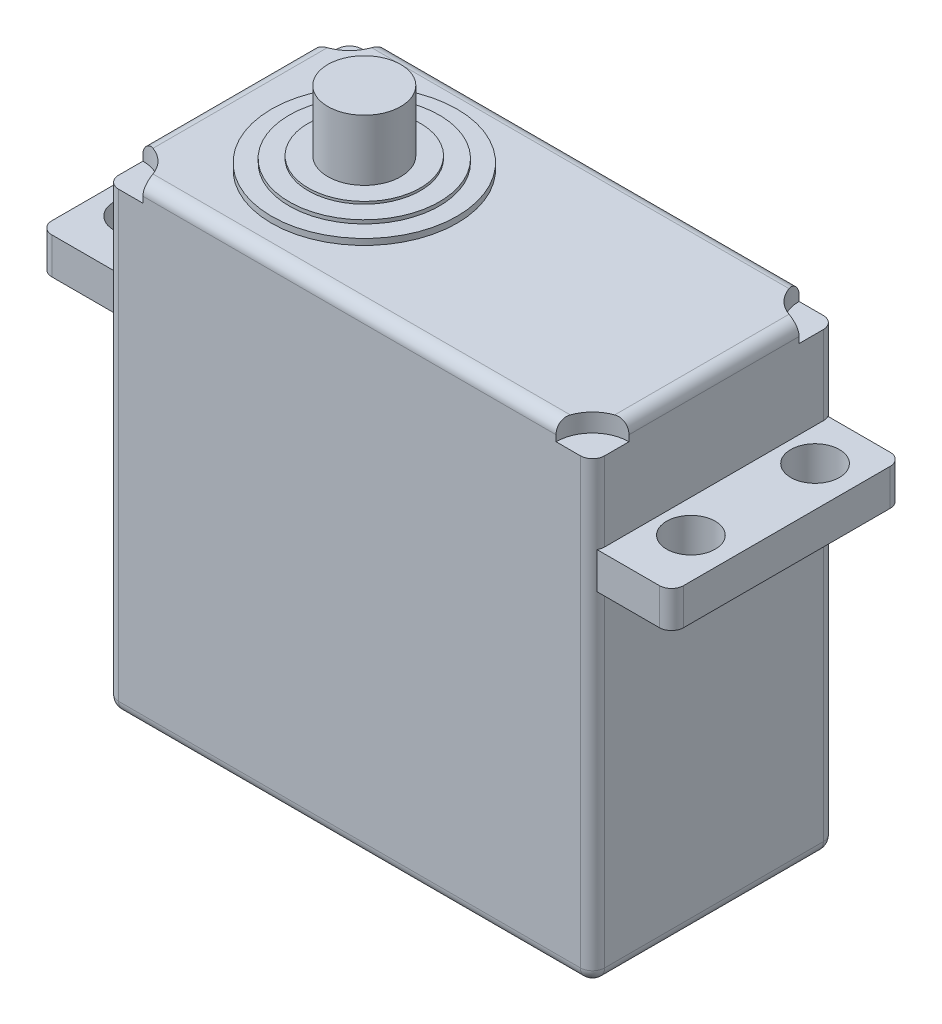
SolidWorks part; units mm, degrees
ref_plane "前视基准面" through (0, 0, 0) normal (0, 0, 1) x (1, 0, 0)
ref_plane "上视基准面" through (0, 0, 0) normal (0, 1, 0) x (1, 0, 0)
ref_plane "右视基准面" through (0, 0, 0) normal (1, 0, 0) x (0, 0, -1)
other "Configuration Table"
sketch "草图1" plane through (0, 0, 0) normal (0, 0, 1) x (1, 0, 0)
  line L1 (-40, 39) -> (0, 39)
  line L2 (-40, 39) -> (-40, 0)
  line L3 (-40, 0) -> (0, 0)
  line L4 (0, 39) -> (0, 0)
  dimension "D1" = 40
  dimension "D2" = 39
extrude "凸台-拉伸1" add sketch "草图1" along normal blind 20
sketch "草图5" plane through (0, 0, 0) normal (0, 1, 0) x (1, 0, 0)
  circle A6 centre (-42.7819, -14.6096) radius 2
  circle A7 centre (-42.8531, -4.6096) radius 2
  circle A8 centre (2.7095, -4.3937) radius 2
  circle A9 centre (2.7095, -14.6096) radius 2
  dimension "D1" = 10
shell "抽壳1" thickness 2
sketch "草图18" plane through (0, 39, 0) normal (0, 1, 0) x (1, 0, 0)
  circle A0 centre (-28.7819, -10) radius 7.6392
  dimension "D1" = 14
extrude "凸台-拉伸8" add sketch "草图18" along normal blind 0.5 contours A0
sketch "草图24" plane through (0, 39.5, 0) normal (0, 1, 0) x (1, 0, 0)
  circle A0 centre (-28.7819, -10) radius 6.1824
extrude "凸台-拉伸12" add sketch "草图24" along normal blind 0.3 contours A0
sketch "草图25" plane through (0, 39.8, 0) normal (0, 1, 0) x (1, 0, 0)
  circle A0 centre (-28.7819, -10) radius 4.6127
extrude "凸台-拉伸13" add sketch "草图25" along normal blind 0.2 contours A0
sketch "草图29" plane through (0, 0, 0) normal (0, 1, 0) x (1, 0, 0)
sketch "草图40" plane through (0, 0, 0) normal (0, 1, 0) x (1, 0, 0)
  line L0 (2.7451, -14.6096) -> (2.7451, -13.3282)
  circle A0 centre (-42.7819, -14.6096) radius 2
sketch "草图48" plane through (0, 0, 0) normal (0, 1, 0) x (1, 0, 0)
sketch "草图52" plane through (0, 40, 0) normal (0, 1, 0) x (1, 0, 0)
  circle A0 centre (-28.7819, -10) radius 3
extrude "凸台-拉伸14" add sketch "草图52" along normal blind 5
sketch "草图55" plane through (0, 39, 0) normal (0, 1, 0) x (1, 0, 0)
  line L0 (-24.75, 0) -> (24.75, 0) construction
  line L1 (-40, -20) -> (-40, 0) construction
  circle A0 centre (-40, -20) radius 3
  circle A1 centre (-40, 0) radius 3
  circle A2 centre (0, -20) radius 3
  circle A3 centre (0, 0) radius 3
extrude "切除-拉伸37" cut sketch "草图55" against normal blind 1.5
sketch "草图78" plane through (0, 0, 0) normal (1, 0, 0) x (0, 0, -1)
  line L0 (-20, 0) -> (0, 0) construction
  line L1 (-19.5, 31) -> (-0.5, 31)
  line L2 (-19.5, 31) -> (-19.5, 28)
  line L3 (-19.5, 28) -> (-0.5, 28)
  line L4 (-0.5, 31) -> (-0.5, 28)
  line L5 (-20, 0) -> (-20, 37.5) construction
  line L6 (0, 24.75) -> (0, -24.75) construction
  point P6 (-19.5, 29.5)
  point P9 (-0.5, 29.5)
  dimension "D1" = 31
  dimension "D2" = 0.5
  dimension "D3" = 0.5
extrude "凸台-拉伸16" add sketch "草图78" along normal blind 6
sketch "草图79" plane through (-40, 0, 0) normal (-1, 0, 0) x (0, 0, 1)
  line L5 (20, 0) -> (0, 0) construction
  line L6 (0.5, 31) -> (19.5, 31)
  line L7 (0.5, 31) -> (0.5, 28)
  line L8 (0.5, 28) -> (19.5, 28)
  line L9 (19.5, 31) -> (19.5, 28)
  dimension "D1" = 31
extrude "凸台-拉伸17" add sketch "草图79" along normal blind 6
fillet "圆角7" radius 1 2 edges at (-46, 29.5, 19.5) (-40, 18.75, 20)
sketch "草图90" plane through (0, 0, 0) normal (0, 1, 0) x (1, 0, 0)
extrude "切除-拉伸45" cut sketch "草图5" along normal blind 50 contours A9 | A8 | A6 | A7
fillet "圆角8" radius 1 15 edges at (-19.5, 0, 20) (-39.7071, 0, 19.7071) (-40, 0, 9.5) (0, 0, 10) (-20, 0, 0) (0, 18.75, 0) (-40, 18.75, 0) (-46, 29.5, 0.5) (6, 29.5, 19.5) (6, 29.5, 0.5) (-20, 39, 0) (0, 39, 10) (0, 18.75, 20) (-40, 39, 10) (-20, 39, 20)
